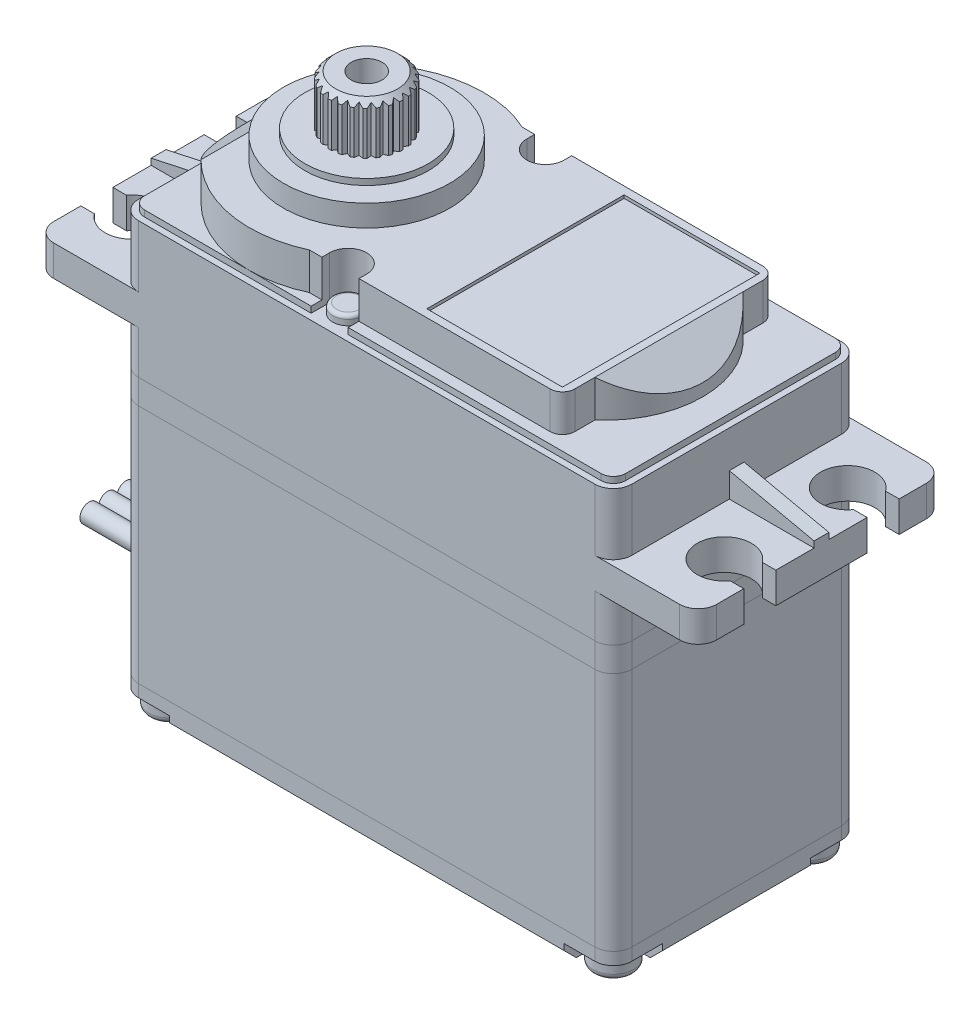
SolidWorks part; units mm, degrees
ref_plane "Front Plane" through (0, 0, 0) normal (0, 0, 1) x (1, 0, 0)
ref_plane "Top Plane" through (0, 0, 0) normal (0, 1, 0) x (1, 0, 0)
ref_plane "Right Plane" through (0, 0, 0) normal (1, 0, 0) x (0, 0, -1)
sketch "Sketch3" plane through (0, 0, 0) normal (0, 1, 0) x (1, 0, 0)
  line L1 (-20, -10) -> (20, -10)
  line L2 (-20, -10) -> (-20, 10)
  line L3 (-20, 10) -> (20, 10)
  line L4 (20, -10) -> (20, 10)
  line L5 (-20, -10) -> (20, 10) construction
  line L6 (-20, 10) -> (20, -10) construction
  point P0 (0, 0)
  dimension "D1" = 40
  dimension "D2" = 20
extrude "Boss-Extrude2" add sketch "Sketch3" against normal blind 27.5 and the other way blind 7.5
sketch "Sketch4" plane through (0, 0, 0) normal (0, 1, 0) x (1, 0, 0)
  line L0 (20, 10) -> (-20, 10) construction
  line L1 (-26.875, -10) -> (26.875, -10)
  line L2 (-26.875, -10) -> (-26.875, 10)
  line L3 (-26.875, 10) -> (26.875, 10)
  line L4 (26.875, -10) -> (26.875, 10)
  line L5 (-26.875, -10) -> (26.875, 10) construction
  line L6 (-26.875, 10) -> (26.875, -10) construction
  point P0 (0, 0)
  dimension "D1" = 53.75
extrude "Boss-Extrude3" add sketch "Sketch4" along normal blind 2.5
sketch "Sketch5" plane through (0, 2.5, 0) normal (0, 1, 0) x (1, 0, 0)
  line L1 (-24, -5) -> (24, -5) construction
  line L2 (-24, -5) -> (-24, 5) construction
  line L3 (-24, 5) -> (24, 5) construction
  line L4 (24, -5) -> (24, 5) construction
  line L5 (-24, -5) -> (24, 5) construction
  line L6 (-24, 5) -> (24, -5) construction
  circle A0 centre (-24, 5) radius 2.2
  circle A1 centre (-24, -5) radius 2.2
  circle A2 centre (24, -5) radius 2.2
  circle A3 centre (24, 5) radius 2.2
  point P0 (0, 0)
  dimension "D3" = 4.4
  dimension "D1" = 10
  dimension "D2" = 48
extrude "Cut-Extrude2" cut sketch "Sketch5" against normal through all
sketch "Sketch6" plane through (0, 2.5, 0) normal (0, 1, 0) x (1, 0, 0)
  line L0 (-24, 5) -> (-26.875, 5) construction
  line L1 (-26.875, 10) -> (-26.875, -10) construction
  line L2 (-24, 3.7) -> (-26.875, 3.7)
  line L3 (-24, 6.3) -> (-26.875, 6.3)
  line L4 (-24, -5) -> (-26.875, -5) construction
  line L5 (-24, -6.3) -> (-26.875, -6.3)
  line L6 (-24, -3.7) -> (-26.875, -3.7)
  line L7 (24, -5) -> (26.875, -5) construction
  line L8 (26.875, -10) -> (26.875, 10) construction
  line L9 (24, -3.7) -> (26.875, -3.7)
  line L10 (24, -6.3) -> (26.875, -6.3)
  line L11 (24, 5) -> (26.875, 5) construction
  line L12 (24, 6.3) -> (26.875, 6.3)
  line L13 (24, 3.7) -> (26.875, 3.7)
  arc A0 (-24, 3.7) -> (-24, 6.3) centre (-24, 5) ccw
  arc A1 (-26.875, 6.3) -> (-26.875, 3.7) centre (-26.875, 5) ccw
  arc A2 (-24, -6.3) -> (-24, -3.7) centre (-24, -5) ccw
  arc A3 (-26.875, -3.7) -> (-26.875, -6.3) centre (-26.875, -5) ccw
  arc A4 (24, -3.7) -> (24, -6.3) centre (24, -5) ccw
  arc A5 (26.875, -6.3) -> (26.875, -3.7) centre (26.875, -5) ccw
  arc A6 (24, 6.3) -> (24, 3.7) centre (24, 5) ccw
  arc A7 (26.875, 3.7) -> (26.875, 6.3) centre (26.875, 5) ccw
  point P5 (-25.4375, 5)
  point P10 (-25.4375, -5)
  point P18 (25.4375, -5)
  point P28 (25.4375, 5)
  dimension "D1" = 2.6
extrude "Cut-Extrude3" cut sketch "Sketch6" against normal through all
fillet "Fillet1" radius 1.5 4 edges at (26.875, 1.25, -10) (26.875, 1.25, 10) (-26.875, 1.25, 10) (-26.875, 1.25, -10)
fillet "Fillet2" radius 1.5 8 edges at (20, -13.75, -10) (20, 5, -10) (20, -13.75, 10) (20, 5, 10) (-20, 5, -10) (-20, -13.75, -10) (-20, 5, 10) (-20, -13.75, 10)
sketch "Sketch7" plane through (0, 7.5, 0) normal (0, 1, 0) x (1, 0, 0)
  line L8 (19.5, -8.5) -> (19.5, 8.5)
  line L9 (18.5, 9.5) -> (-18.5, 9.5)
  line L10 (-19.5, 8.5) -> (-19.5, -8.5)
  line L11 (-18.5, -9.5) -> (18.5, -9.5)
  line L12 (19.5, -8.5) -> (19.5, 8.5)
  line L13 (18.5, 9.5) -> (-18.5, 9.5)
  line L14 (-19.5, 8.5) -> (-19.5, -8.5)
  line L15 (-18.5, -9.5) -> (18.5, -9.5)
  arc A8 (19.5, 8.5) -> (18.5, 9.5) centre (18.5, 8.5) ccw
  arc A9 (-18.5, 9.5) -> (-19.5, 8.5) centre (-18.5, 8.5) ccw
  arc A10 (-19.5, -8.5) -> (-18.5, -9.5) centre (-18.5, -8.5) ccw
  arc A11 (18.5, -9.5) -> (19.5, -8.5) centre (18.5, -8.5) ccw
  arc A12 (19.5, 8.5) -> (18.5, 9.5) centre (18.5, 8.5) ccw
  arc A13 (-18.5, 9.5) -> (-19.5, 8.5) centre (-18.5, 8.5) ccw
  arc A14 (-19.5, -8.5) -> (-18.5, -9.5) centre (-18.5, -8.5) ccw
  arc A15 (18.5, -9.5) -> (19.5, -8.5) centre (18.5, -8.5) ccw
  dimension "D1" = 0.5
extrude "Boss-Extrude4" add sketch "Sketch7" along normal blind 0.5
sketch "Sketch8" plane through (0, 0, 0) normal (0, 0, 1) x (1, 0, 0)
  line L0 (20, 4.5) -> (26.875, 3)
  line L1 (20, 7.5) -> (20, 2.5) construction
  line L2 (26.875, 3) -> (26.875, 2.5)
  line L3 (26.875, 2.5) -> (20, 2.5)
  line L4 (20, 2.5) -> (20, 4.5)
  line L5 (18.5, 0) -> (25.375, 0) construction
  line L6 (-26.875, 2.5) -> (-26.875, 3)
  line L7 (-26.875, 3) -> (-20, 4.5)
  line L8 (-20, 2.5) -> (-20, 7.5) construction
  line L9 (-20, 4.5) -> (-20, 2.5)
  line L10 (-20, 2.5) -> (-26.875, 2.5)
  dimension "D1" = 0.5
  dimension "D2" = 4.5
extrude "Boss-Extrude5" add sketch "Sketch8" along normal mid plane 1.2
sketch "Sketch9" plane through (0, 8, 0) normal (0, 1, 0) x (1, 0, 0)
  line L0 (-19.5, 8.5) -> (-19.5, -8.5) construction
  line L1 (18.5, 9.5) -> (-18.5, 9.5) construction
  line L2 (-18.5, -9.5) -> (18.5, -9.5) construction
  line L3 (-6.0176, 8.625) -> (14.5, 8.625)
  line L4 (14.5, 8.625) -> (14.5, 6)
  line L5 (-6.0176, -8.625) -> (14.5, -8.625)
  line L6 (14.5, -8.625) -> (14.5, -6)
  line L7 (-19.5, 0) -> (17.25, 0) construction
  line L8 (20, -8.5) -> (20, 8.5) construction
  arc A0 (-6.0176, 8.625) -> (-6.0176, -8.625) centre (-10, 0) ccw
  arc A1 (14.5, 6) -> (14.5, -6) centre (9.3295, 0) cw
  dimension "D1" = 17.25
  dimension "D2" = 12
  dimension "D3" = 36.75
  dimension "D4" = 5.5
extrude "Boss-Extrude6" add sketch "Sketch9" along normal blind 3
sketch "Sketch10" plane through (0, 11, 0) normal (0, 1, 0) x (1, 0, 0)
  circle A0 centre (-10, 0) radius 6.75
  dimension "D1" = 13.5
extrude "Boss-Extrude7" add sketch "Sketch10" along normal blind 1.75
sketch "Sketch11" plane through (0, 0, 0) normal (0, 0, 1) x (1, 0, 0)
  line L0 (14.5, 11) -> (17.25, 9)
  line L1 (17.25, 8) -> (17.25, 11) construction
  line L2 (17.25, 9) -> (17.25, 11)
  line L3 (17.25, 11) -> (14.5, 11) construction
  line L4 (17.25, 11) -> (14.5, 11)
  line L5 (-10, 8) -> (18.5, 8) construction
  line L6 (-16.75, 11) -> (-19.5, 9)
  line L7 (-19.5, 9) -> (-19.5, 11)
  line L8 (-19.5, 11) -> (-16.75, 11)
  line L9 (-18.5, 8) -> (-10, 8) construction
  dimension "D1" = 1
  dimension "D2" = 1
extrude "Cut-Extrude4" cut sketch "Sketch11" against normal through all both and the other way through all
fillet "Fillet3" radius 1 2 edges at (14.5, 9.5, -8.625) (14.5, 9.5, 8.625)
sketch "Sketch12" plane through (0, 12.75, 0) normal (0, 1, 0) x (1, 0, 0)
  circle A0 centre (-10, 0) radius 5
  dimension "D1" = 10
extrude "Boss-Extrude8" add sketch "Sketch12" along normal blind 0.5
ref_plane "Plane2" through (0, -3.5, 0) normal (0, 1, 0) x (1, 0, 0)
split "Split1" trim tools "Plane2" bodies to split 115 resulting bodies 116 117
ref_plane "Plane3" through (0, -5.5, 0) normal (0, 1, 0) x (1, 0, 0)
split "Split2" trim tools "Plane3" bodies to split 117 resulting bodies 118 119
ref_plane "Plane4" through (0, -25, 0) normal (0, -1, 0) x (-1, 0, 0)
split "Split3" trim tools "Plane4" bodies to split 119 resulting bodies 120 121
sketch "Sketch13" plane through (0, 11, 0) normal (0, 1, 0) x (1, 0, 0)
  line L0 (-3.5, 8) -> (-3.5, -8) construction
  line L1 (-3.5, 0) -> (-10, 0) construction
  line L2 (14.5, -7.625) -> (14.5, -6) construction
  line L3 (-3.5, -8) -> (-3.5, -9.5) construction
  line L5 (-2, -8) -> (-2, -9.5)
  line L6 (-5, -8) -> (-5, -9.5)
  line L7 (-3.5, 8) -> (-3.5, 9.5) construction
  line L9 (-5, 8) -> (-5, 9.5)
  line L10 (-2, 8) -> (-2, 9.5)
  line L11 (18.5, 9.5) -> (-18.5, 9.5) construction
  circle A0 centre (-3.5, 8) radius 1.5 construction
  circle A1 centre (-3.5, -8) radius 1.5 construction
  arc A2 (-2, -8) -> (-5, -8) centre (-3.5, -8) ccw
  arc A3 (-5, -9.5) -> (-2, -9.5) centre (-3.5, -9.5) ccw
  arc A4 (-5, 8) -> (-2, 8) centre (-3.5, 8) ccw
  arc A5 (-2, 9.5) -> (-5, 9.5) centre (-3.5, 9.5) ccw
  point P12 (-3.5, -8.75)
  point P17 (-3.5, 8.75)
  dimension "D2" = 3
  dimension "D1" = 16
  dimension "D3" = 18
extrude "Cut-Extrude5" cut sketch "Sketch13" against normal up to surface (3.5 mm away) up to face at (0, 7.5, 0)
sketch "Sketch15" plane through (0, -27.5, 0) normal (0, -1, 0) x (1, 0, 0)
  line L0 (-20, -8.5) -> (-20, 8.5) construction
  line L1 (-20, 6) -> (-18, 6)
  line L2 (-20, 6) -> (-20, 10)
  line L3 (-20, 10) -> (-16, 10)
  line L4 (-16, 8) -> (-16, 10)
  line L5 (-18.5, 10) -> (18.5, 10) construction
  line L6 (18.5, -10) -> (-18.5, -10) construction
  line L7 (-20, -6) -> (-18, -6)
  line L8 (-20, -6) -> (-20, -10)
  line L9 (-20, -10) -> (-16, -10)
  line L10 (-16, -8) -> (-16, -10)
  line L11 (20, -8.5) -> (20, 8.5) construction
  line L12 (16, -10) -> (20, -10)
  line L13 (16, -10) -> (16, -8)
  line L14 (18, -6) -> (20, -6)
  line L15 (20, -10) -> (20, -6)
  line L17 (20, 6) -> (18, 6)
  line L18 (20, 6) -> (20, 10)
  line L19 (20, 10) -> (16, 10)
  line L20 (16, 8) -> (16, 10)
  arc A0 (18, 6) -> (16, 8) centre (18, 8) cw
  arc A1 (16, -8) -> (18, -6) centre (18, -8) cw
  arc A2 (-18, -6) -> (-16, -8) centre (-18, -8) cw
  arc A3 (-18, 6) -> (-16, 8) centre (-18, 8) ccw
  dimension "D3" = 2
  dimension "D1" = 4
  dimension "D2" = 4
extrude "Cut-Extrude6" cut sketch "Sketch15" against normal blind 1.5
chamfer "Chamfer3" distance 1 angle 45 4 edges at (20, -27.5, 0) (0, -27.5, 10) (0, -27.5, -10) (-20, -27.5, 0)
sketch "Sketch16" plane through (-20, 0, 0) normal (-1, 0, 0) x (0, 0, 1)
  line L0 (0, -21.5) -> (0, 0) construction
  line L1 (-3.5, -21.5) -> (3.5, -21.5)
  line L2 (-3.5, -21.5) -> (-3.5, -25.5)
  line L3 (-3.5, -25.5) -> (3.5, -25.5)
  line L4 (3.5, -21.5) -> (3.5, -25.5)
  line L5 (6, -27.5) -> (-6, -27.5) construction
  dimension "D1" = 4
  dimension "D2" = 2
  dimension "D3" = 7
extrude "Boss-Extrude9" add sketch "Sketch16" along normal blind 1 separate body
sketch "Sketch17" plane through (-21, 0, 0) normal (-1, 0, 0) x (0, 0, 1)
  line L8 (-3.25, -21.75) -> (-3.25, -25.25)
  line L9 (-3.25, -25.25) -> (3.25, -25.25)
  line L10 (3.25, -25.25) -> (3.25, -21.75)
  line L11 (3.25, -21.75) -> (-3.25, -21.75)
  line L12 (-3.25, -21.75) -> (-3.25, -25.25)
  line L13 (-3.25, -25.25) -> (3.25, -25.25)
  line L14 (3.25, -25.25) -> (3.25, -21.75)
  line L15 (3.25, -21.75) -> (-3.25, -21.75)
  dimension "D1" = 0.25
ref_plane "Plane5" through (-26, 0, 0) normal (-1, 0, 0) x (0, 0, 1)
sketch "Sketch18" plane through (-26, 0, 0) normal (-1, 0, 0) x (0, 0, 1)
  line L0 (-3.5, -25.5) -> (3.5, -21.5) construction
  line L2 (-2.5, -24.75) -> (2.5, -24.75)
  line L3 (-2.5, -24.75) -> (-2.5, -22.25)
  line L4 (-2.5, -22.25) -> (2.5, -22.25)
  line L5 (2.5, -24.75) -> (2.5, -22.25)
  line L6 (-2.5, -24.75) -> (2.5, -22.25) construction
  line L7 (-2.5, -22.25) -> (2.5, -24.75) construction
  point P4 (0, -23.5)
  dimension "D1" = 5
  dimension "D2" = 2.5
loft "Loft1" add profiles "Sketch17", "Sketch18"
sketch "Sketch19" plane through (-26, 0, 0) normal (-1, 0, 0) x (0, 0, 1)
  line L0 (0, -24.75) -> (0, -23.5) construction
  line L1 (-2.5, -24.75) -> (2.5, -24.75) construction
  line L2 (0, -23.5) -> (0, -22.25) construction
  line L3 (2.5, -22.25) -> (-2.5, -22.25) construction
  circle A0 centre (0, -23.5) radius 0.75
  circle A1 centre (1.5, -23.5) radius 0.75
  circle A2 centre (-1.5, -23.5) radius 0.75
  dimension "D1" = 1.5
extrude "Boss-Extrude11" add sketch "Sketch19" along normal blind 5 separate body contours A2 | A0 | A1 region at (-26, -23.5, 0) region at (-26, -23.5, -1.5) region at (-26, -23.5, 1.5)
sketch "Sketch20" plane through (0, 11, 0) normal (0, 1, 0) x (1, 0, 0)
  line L0 (-10, 0) -> (2.875, 0) construction
  line L1 (2.875, -8) -> (13.875, -8)
  line L2 (2.875, -8) -> (2.875, 8)
  line L3 (2.875, 8) -> (13.875, 8)
  line L4 (13.875, -8) -> (13.875, 8)
  line L5 (2.875, -8) -> (13.875, 8) construction
  line L6 (2.875, 8) -> (13.875, -8) construction
  line L7 (8.375, 8) -> (8.375, 8.625) construction
  line L8 (13.5, 8.625) -> (-2, 8.625) construction
  line L9 (13.875, 6.9566) -> (14.5, 6.9566) construction
  line L10 (14.5, 6) -> (14.5, 7.625) construction
  point P0 (8.375, 0)
  dimension "D1" = 16
  dimension "D2" = 11
extrude "Cut-Extrude7" cut sketch "Sketch20" against normal blind 0.25
sketch "Sketch21" plane through (0, 13.25, 0) normal (0, 1, 0) x (1, 0, 0)
  circle A0 centre (-10, 0) radius 3
  dimension "D1" = 6
extrude "Boss-Extrude12" add sketch "Sketch21" along normal blind 4 separate body
chamfer "Chamfer4" distance 0.5 angle 45 1 edges at (-10, 17.25, 3)
sketch "Sketch22" plane through (0, 17.25, 0) normal (0, 1, 0) x (1, 0, 0)
  line L0 (-10.25, 2.9896) -> (-10, 2.75)
  line L1 (-10, 2.75) -> (-9.75, 2.9896)
  line L2 (-10, 0) -> (-10, 2.75) construction
  line L3 (-10, 2.75) -> (-10, 3) construction
  arc A1 (-9.75, 2.9896) -> (-10.25, 2.9896) centre (-10, 0) ccw
  circle A2 centre (-10, 0) radius 3 construction
  dimension "D1" = 0.25
  dimension "D2" = 0.5
extrude "Cut-Extrude8" cut sketch "Sketch22" against normal up to surface (4 mm away) up to face at (-10, 13.25, 5)
pattern_circular "CirPattern1" count 25 over 360 about axis through (-10, 17.25, 0) along (0, -1, 0) of "Cut-Extrude8"
hole_wizard "M3x0.5 Tapped Hole1" positions "Sketch23" profile "Sketch25" tap size "M3x0.5" standard "ANSI Metric"
sketch "Sketch23" plane through (0, 17.25, 0) normal (0, 1, 0) x (1, 0, 0)
  point P0 (-10, 0)
sketch "Sketch25" plane through (-10, 17.25, 0) normal (1, 0, 0) x (0, 0, 1)
  line L0 (0, 0) -> (0, 9.2511)
  line L1 (0, 9.2511) -> (1.25, 8.5)
  line L2 (1.25, 8.5) -> (1.25, 0)
  line L5 (1.25, 0) -> (0, 0)
  line L10 (0, 9.2511) -> (-1.25, 8.5) construction
  line L11 (0, -6.35) -> (0, 107.95) construction
  dimension "Tap Drill Dia." = 2.5
  dimension "Tap Drill Depth" = 8.5
  dimension "Drill Angle" = 118
ref_plane "Plane6" through (0, -21, 0) normal (0, -1, 0) x (-1, 0, 0)
sketch "Sketch26" plane through (0, -26, 0) normal (0, -1, 0) x (1, 0, 0)
  line L0 (18, -8) -> (18, -10) construction
  line L1 (16, -10) -> (18.5, -10) construction
  line L2 (18, -8) -> (20, -8) construction
  line L3 (20, -8.5) -> (20, -6) construction
  line L5 (-18, 8) -> (18, 8) construction
  line L6 (-18, 8) -> (-18, -8) construction
  line L7 (-18, -8) -> (18, -8) construction
  line L8 (18, 8) -> (18, -8) construction
  line L9 (-18, 8) -> (18, -8) construction
  line L10 (-18, -8) -> (18, 8) construction
  circle A0 centre (18, -8) radius 1.65
  arc A1 (18, -6) -> (16, -8) centre (18, -8) ccw construction
  circle A2 centre (-18, -8) radius 1.65
  circle A3 centre (-18, 8) radius 1.65
  circle A4 centre (18, 8) radius 1.65
  point P8 (0, 0)
  dimension "D1" = 3.3
extrude "Boss-Extrude13" add sketch "Sketch26" along normal up to surface (1.5 mm away) up to face at (0, -27.5, 0)
fillet "Fillet4" radius 0.5 4 edges at (-18, -27.5, -9.65) (-18, -27.5, 6.35) (18, -27.5, 6.35) (18, -27.5, -9.65)
sketch "Sketch27" plane through (0, -21, 0) normal (0, -1, 0) x (-1, 0, 0)
  line L0 (0, 0) -> (-50000, 0) construction
  line L2 (-16, -9) -> (16, -9) construction
  line L3 (-19, 6) -> (-19, -6) construction
  line L4 (6.5, -8.5) -> (6.5, -9) construction
  line L5 (-3.5, -7.5) -> (-3.5, -9) construction
  line L6 (20, -8.5) -> (20, 8.5) construction
  line L11 (18.5, 10) -> (-18.5, 10)
  line L12 (20, -8.5) -> (20, 8.5)
  line L13 (-18.5, -10) -> (18.5, -10)
  line L14 (-20, 8.5) -> (-20, -8.5)
  line L15 (18.5, 10) -> (-18.5, 10)
  line L16 (20, -8.5) -> (20, 8.5)
  line L17 (-18.5, -10) -> (18.5, -10)
  line L18 (-20, 8.5) -> (-20, -8.5)
  circle A0 centre (-18, 8) radius 1.15 construction
  circle A1 centre (-18, -8) radius 1.15 construction
  circle A2 centre (18, -8) radius 1.15 construction
  circle A3 centre (18, 8) radius 1.15 construction
  circle A4 centre (-18, 8) radius 1.15
  circle A5 centre (-18, -8) radius 1.15
  circle A6 centre (18, -8) radius 1.15
  circle A7 centre (18, 8) radius 1.15
  arc A8 (10, 9) -> (10, -9) centre (10, 0) cw
  arc A9 (10, -9) -> (8.4576, -8.7797) centre (10, -3.4916) cw
  arc A10 (8.4576, -8.7797) -> (4.5424, -8.7797) centre (6.5, -15.4916) ccw
  arc A11 (4.5424, -8.7797) -> (0.5862, -8.443) centre (3, -3.4916) cw
  arc A12 (0.5862, -8.443) -> (-7.5862, -8.443) centre (-3.5, -16.8249) ccw
  arc A13 (-7.5862, -8.443) -> (-10, -9) centre (-10, -3.4916) cw
  arc A14 (-10, -9) -> (-10, 9) centre (-10, 0) cw
  arc A15 (10, 9) -> (8.4576, 8.7797) centre (10, 3.4916) ccw
  arc A16 (8.4576, 8.7797) -> (4.5424, 8.7797) centre (6.5, 15.4916) cw
  arc A17 (4.5424, 8.7797) -> (0.5862, 8.443) centre (3, 3.4916) ccw
  arc A18 (0.5862, 8.443) -> (-7.5862, 8.443) centre (-3.5, 16.8249) cw
  arc A19 (-7.5862, 8.443) -> (-10, 9) centre (-10, 3.4916) ccw
  arc A24 (-18.5, 10) -> (-20, 8.5) centre (-18.5, 8.5) ccw
  arc A25 (20, 8.5) -> (18.5, 10) centre (18.5, 8.5) ccw
  arc A26 (18.5, -10) -> (20, -8.5) centre (18.5, -8.5) ccw
  arc A27 (-20, -8.5) -> (-18.5, -10) centre (-18.5, -8.5) ccw
  arc A28 (-18.5, 10) -> (-20, 8.5) centre (-18.5, 8.5) ccw
  arc A29 (20, 8.5) -> (18.5, 10) centre (18.5, 8.5) ccw
  arc A30 (18.5, -10) -> (20, -8.5) centre (18.5, -8.5) ccw
  arc A31 (-20, -8.5) -> (-18.5, -10) centre (-18.5, -8.5) ccw
  dimension "D1" = 10
  dimension "D2" = 0.5
  dimension "D3" = 1.5
  dimension "D4" = 13.5
  dimension "D5" = 23.5
  dimension "D6" = 0
extrude "Cut-Extrude9" cut sketch "Sketch27" against normal blind 13
sketch "Sketch28" plane through (0, -21, 0) normal (0, 1, 0) x (1, 0, 0)
  line L4 (18.5, 10) -> (-18.5, 10)
  line L5 (-20, 8.5) -> (-20, -8.5)
  line L6 (-18.5, -10) -> (18.5, -10)
  line L7 (20, -8.5) -> (20, 8.5)
  line L8 (18.5, 10) -> (-18.5, 10)
  line L9 (-20, 8.5) -> (-20, -8.5)
  line L10 (-18.5, -10) -> (18.5, -10)
  line L11 (20, -8.5) -> (20, 8.5)
  arc A4 (20, 8.5) -> (18.5, 10) centre (18.5, 8.5) ccw
  arc A5 (-18.5, 10) -> (-20, 8.5) centre (-18.5, 8.5) ccw
  arc A6 (-20, -8.5) -> (-18.5, -10) centre (-18.5, -8.5) ccw
  arc A7 (18.5, -10) -> (20, -8.5) centre (18.5, -8.5) ccw
  arc A8 (20, 8.5) -> (18.5, 10) centre (18.5, 8.5) ccw
  arc A9 (-18.5, 10) -> (-20, 8.5) centre (-18.5, 8.5) ccw
  arc A10 (-20, -8.5) -> (-18.5, -10) centre (-18.5, -8.5) ccw
  arc A11 (18.5, -10) -> (20, -8.5) centre (18.5, -8.5) ccw
  dimension "D1" = 0
extrude "Boss-Extrude14" add sketch "Sketch28" along normal blind 1.2 from offset 1.2
pattern_linear "LPattern1" count 5 spacing 2.4 along (0, 1, 0) of "Boss-Extrude14"
sketch "Sketch29" plane through (0, 7.5, 0) normal (0, 1, 0) x (1, 0, 0)
  circle A0 centre (-3.5, -8) radius 1.25
  circle A1 centre (-3.5, 8) radius 1.25
  dimension "D1" = 2.5
extrude "Boss-Extrude15" add sketch "Sketch29" along normal blind 0.75
fillet "Fillet5" radius 0.3 2 edges at (-3.5, 8.25, -6.75) (-3.5, 8.25, 9.25)
sketch "Sketch30" plane through (0, -8, 0) normal (0, -1, 0) x (1, 0, 0)
  line L4 (20, -8.5) -> (20, 8.5)
  line L5 (18.5, 10) -> (-18.5, 10)
  line L6 (-20, 8.5) -> (-20, -8.5)
  line L7 (-18.5, -10) -> (18.5, -10)
  line L8 (20, -8.5) -> (20, 8.5)
  line L9 (18.5, 10) -> (-18.5, 10)
  line L10 (-20, 8.5) -> (-20, -8.5)
  line L11 (-18.5, -10) -> (18.5, -10)
  arc A4 (18.5, -10) -> (20, -8.5) centre (18.5, -8.5) ccw
  arc A5 (20, 8.5) -> (18.5, 10) centre (18.5, 8.5) ccw
  arc A6 (-18.5, 10) -> (-20, 8.5) centre (-18.5, 8.5) ccw
  arc A7 (-20, -8.5) -> (-18.5, -10) centre (-18.5, -8.5) ccw
  arc A8 (18.5, -10) -> (20, -8.5) centre (18.5, -8.5) ccw
  arc A9 (20, 8.5) -> (18.5, 10) centre (18.5, 8.5) ccw
  arc A10 (-18.5, 10) -> (-20, 8.5) centre (-18.5, 8.5) ccw
  arc A11 (-20, -8.5) -> (-18.5, -10) centre (-18.5, -8.5) ccw
  dimension "D1" = 0
extrude "Boss-Extrude16" add sketch "Sketch30" along normal up to surface (13 mm away) up to face at (-0.9987, -21, 0)
